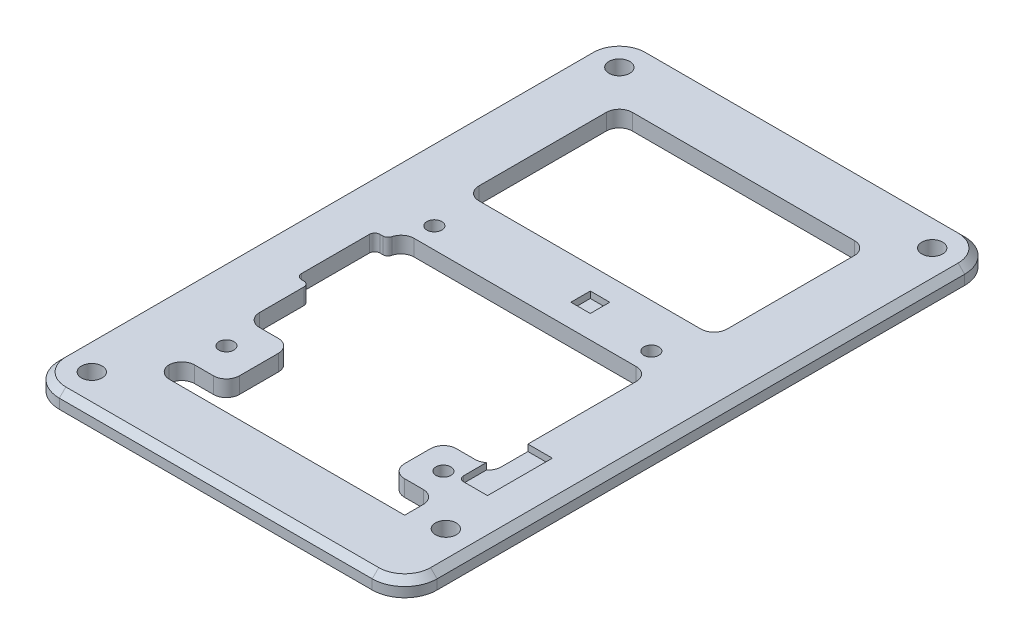
SolidWorks part; units mm, degrees
ref_plane "Front Plane" through (0, 0, 0) normal (0, 0, 1) x (1, 0, 0)
ref_plane "Top Plane" through (0, 0, 0) normal (0, 1, 0) x (1, 0, 0)
ref_plane "Right Plane" through (0, 0, 0) normal (1, 0, 0) x (0, 0, -1)
sketch "Sketch1" plane through (0, 0, 0) normal (0, 1, 0) x (1, 0, 0)
  line L4 (26.75, 55.875) -> (-26.75, 55.875)
  line L5 (26.75, -45.825) -> (26.75, 55.875)
  line L6 (-26.75, -45.825) -> (26.75, -45.825)
  line L7 (-26.75, 55.875) -> (-26.75, -45.825)
  line L8 (26.75, 55.875) -> (-26.75, 55.875)
  line L9 (26.75, -45.825) -> (26.75, 55.875)
  line L10 (-26.75, -45.825) -> (26.75, -45.825)
  line L11 (-26.75, 55.875) -> (-26.75, -45.825)
  line L12 (3.325, 28.475) -> (-2.675, 28.475)
  line L13 (3.325, 24.185) -> (3.325, 28.475)
  line L14 (-2.675, 24.185) -> (3.325, 24.185)
  line L15 (-2.675, 28.475) -> (-2.675, 24.185)
  line L16 (3.325, 28.475) -> (-2.675, 28.475)
  line L17 (3.325, 24.185) -> (3.325, 28.475)
  line L18 (-2.675, 24.185) -> (3.325, 24.185)
  line L19 (-2.675, 28.475) -> (-2.675, 24.185)
  line L20 (-2.675, 4.275) -> (3.325, 4.275)
  line L21 (3.325, 4.275) -> (3.325, 8.565)
  line L22 (3.325, 8.565) -> (-2.675, 8.565)
  line L23 (-2.675, 8.565) -> (-2.675, 4.275)
  line L24 (-2.675, 4.275) -> (3.325, 4.275)
  line L25 (3.325, 4.275) -> (3.325, 8.565)
  line L26 (3.325, 8.565) -> (-2.675, 8.565)
  line L27 (-2.675, 8.565) -> (-2.675, 4.275)
  circle A1 centre (24.125, -34.325) radius 1.5
  circle A2 centre (24.125, -34.325) radius 1.5
  circle A3 centre (-24.125, -40.675) radius 1.5
  circle A4 centre (-24.125, -40.675) radius 1.5
  circle A5 centre (24.125, 40.675) radius 1.5
  circle A6 centre (24.125, 40.675) radius 1.5
  circle A7 centre (-24.125, 40.675) radius 1.5
  circle A8 centre (-24.125, 40.675) radius 1.5
  dimension "D1" = 0
  dimension "D2" = 0
  dimension "D3" = 0
  dimension "D4" = 0
  dimension "D5" = 0
  dimension "D6" = 0
  dimension "D7" = 0
sketch "Sketch2" plane through (0, 0, 0) normal (0, 1, 0) x (1, 0, 0)
  line L0 (-24.125, 40.675) -> (24.125, 40.675) construction
  line L1 (24.125, 40.675) -> (24.125, -40.675) construction
  line L2 (24.125, -40.675) -> (-24.125, -40.675) construction
  line L3 (-24.125, -40.675) -> (-24.125, 40.675) construction
  line L4 (-29.125, -45.675) -> (-29.125, 45.675)
  line L5 (-29.125, 45.675) -> (29.125, 45.675)
  line L6 (29.125, 45.675) -> (29.125, -45.675)
  line L7 (29.125, -45.675) -> (-29.125, -45.675)
  line L8 (-19.125, -35.675) -> (-19.125, 35.675)
  line L9 (-19.125, 35.675) -> (19.125, 35.675)
  line L10 (19.125, 35.675) -> (19.125, -35.675)
  line L11 (19.125, -35.675) -> (-19.125, -35.675)
  circle A0 centre (24.125, 40.675) radius 1.5 construction
  circle A1 centre (24.125, -34.325) radius 1.5 construction
  circle A2 centre (-24.125, -40.675) radius 1.5 construction
  circle A3 centre (-24.125, 40.675) radius 1.5 construction
  circle A4 centre (24.125, 40.675) radius 1.5
  circle A5 centre (24.125, -34.325) radius 1.5
  circle A6 centre (-24.125, -40.675) radius 1.5
  circle A7 centre (-24.125, 40.675) radius 1.5
  dimension "D1" = 5
  dimension "D2" = 5
sketch "Sketch3" plane through (0, 0, 0) normal (0, 1, 0) x (1, 0, 0)
  line L0 (29.125, -45.675) -> (-29.125, -45.675) construction
  line L1 (-23.5, 9.325) -> (23.5, 9.325)
  line L2 (-23.5, 9.325) -> (-23.5, -30.675)
  line L3 (-23.5, -30.675) -> (23.5, -30.675)
  line L4 (23.5, 9.325) -> (23.5, -30.675)
  line L5 (-23.5, 9.325) -> (23.5, -30.675)
  line L6 (-23.5, -30.675) -> (23.5, 9.325)
  line L7 (-20.5, -0.675) -> (-14.9, -0.675)
  line L8 (-20.5, -0.675) -> (-20.5, -11.575)
  line L9 (-20.5, -11.575) -> (-14.9, -11.575)
  line L10 (-14.9, -0.675) -> (-14.9, -11.575)
  line L11 (5.2, -6.775) -> (16.8, -6.775)
  line L12 (5.2, -6.775) -> (5.2, -21.775)
  line L13 (5.2, -21.775) -> (16.8, -21.775)
  line L14 (16.8, -6.775) -> (16.8, -21.775)
  line L16 (18.4, -16.675) -> (22.9, -16.675)
  line L18 (18.4, -16.675) -> (18.4, -26.675)
  line L19 (18.4, -26.675) -> (22.9, -26.675)
  line L20 (22.9, -16.675) -> (22.9, -26.675)
  line L21 (3.5, 8.575) -> (6.5, 8.575)
  line L22 (3.5, 8.575) -> (3.5, 5.575)
  line L23 (3.5, 5.575) -> (6.5, 5.575)
  line L24 (6.5, 8.575) -> (6.5, 5.575)
  circle A0 centre (-17.23, -26.805) radius 1.27
  circle A1 centre (16.23, -26.805) radius 1.27
  circle A2 centre (-17.23, 5.255) radius 1.27
  circle A3 centre (16.23, 5.255) radius 1.27
  point P0 (0, -10.675)
  point P21 (16.23, 6.525)
  point P23 (-18.5, 5.255)
  point P24 (17.5, 5.255)
  point P27 (16.23, -28.075)
  dimension "D15" = 2.54
  dimension "D1" = 47
  dimension "D2" = 40
  dimension "D3" = 10.9
  dimension "D4" = 5.6
  dimension "D5" = 3
  dimension "D6" = 10
  dimension "D7" = 11.6
  dimension "D8" = 15
  dimension "D9" = 8.9
  dimension "D10" = 6.7
  dimension "D11" = 5
  dimension "D12" = 6
  dimension "D13" = 2.8
  dimension "D14" = 2.6
  dimension "D16" = 15
  dimension "D17" = 10
  dimension "D18" = 4
  dimension "D19" = 0.6
  dimension "D20" = 4.5
  dimension "D21" = 3
  dimension "D22" = 0.75
  dimension "D23" = 17
sketch "Sketch5" plane through (0, 0, 0) normal (0, 1, 0) x (1, 0, 0)
  line L0 (-19.125, 2.025) -> (19.125, 2.025)
  line L1 (-23.5, 9.325) -> (23.5, 9.325) construction
  line L2 (-19.125, 12.025) -> (19.125, 12.025)
  line L3 (-19.125, 2.025) -> (-19.125, -21.805)
  line L4 (-19.125, 35.675) -> (-19.125, -35.675)
  line L5 (19.125, 35.675) -> (-19.125, 35.675)
  line L6 (19.125, -35.675) -> (19.125, 35.675)
  line L7 (-19.125, -35.675) -> (19.125, -35.675)
  line L8 (-19.125, 35.675) -> (-19.125, 12.025)
  line L9 (19.125, 35.675) -> (-19.125, 35.675)
  line L10 (19.125, -35.675) -> (19.125, -30.805)
  line L11 (-19.125, -35.675) -> (19.125, -35.675)
  line L12 (29.125, -45.675) -> (29.125, 45.675)
  line L13 (29.125, 45.675) -> (-29.125, 45.675)
  line L14 (-29.125, 45.675) -> (-29.125, -45.675)
  line L15 (-29.125, -45.675) -> (29.125, -45.675)
  line L16 (29.125, -45.675) -> (29.125, 45.675)
  line L17 (29.125, 45.675) -> (-29.125, 45.675)
  line L18 (-29.125, 45.675) -> (-29.125, -45.675)
  line L19 (-29.125, -45.675) -> (29.125, -45.675)
  line L20 (19.125, 12.025) -> (19.125, 35.675)
  line L21 (-19.125, -31.805) -> (-19.125, -35.675)
  line L22 (-19.125, -21.805) -> (-12.23, -21.805)
  line L28 (-19.125, -31.805) -> (-12.23, -31.805)
  line L29 (-12.23, -21.805) -> (-12.23, -31.805)
  line L30 (19.125, -22.805) -> (12.23, -22.805)
  line L32 (19.125, -30.805) -> (12.23, -30.805)
  line L33 (12.23, -22.805) -> (12.23, -30.805)
  line L34 (19.125, -22.805) -> (19.125, 2.025)
  line L35 (16.23, -26.805) -> (16.23, -30.805) construction
  line L36 (16.23, -26.805) -> (12.23, -26.805) construction
  line L37 (-17.23, -26.805) -> (-12.23, -26.805) construction
  line L39 (-17.23, -26.805) -> (-17.23, -31.805) construction
  circle A0 centre (-17.23, 5.255) radius 1.15
  circle A2 centre (-24.125, 40.675) radius 1.6
  circle A4 centre (-24.125, -40.675) radius 1.6
  circle A6 centre (24.125, -34.325) radius 1.6
  circle A8 centre (24.125, 40.675) radius 1.6
  circle A9 centre (-17.23, -26.805) radius 1.27
  circle A10 centre (-17.23, -26.805) radius 1.27 construction
  circle A11 centre (16.23, 5.255) radius 1.27
  circle A12 centre (16.23, 5.255) radius 1.27 construction
  circle A13 centre (-17.23, 5.255) radius 1.27
  circle A14 centre (-17.23, 5.255) radius 1.27 construction
  circle A15 centre (16.23, -26.805) radius 1.27
  circle A16 centre (16.23, -26.805) radius 1.27 construction
  circle A17 centre (16.23, 5.255) radius 1.15
  circle A18 centre (16.23, -26.805) radius 1.15
  circle A19 centre (-17.23, -26.805) radius 1.15
  point P3 (12.23, -23.8522)
  point P46 (12.23, -26.805)
  point P47 (-12.23, -26.805)
  dimension "D14" = 2.3
  dimension "D2" = 3.2
  dimension "D11" = 7.3
  dimension "D12" = 10
  dimension "D3" = 10
  dimension "D4" = 8
  dimension "D5" = 0
  dimension "D6" = 0
  dimension "D7" = 0
  dimension "D8" = 0
  dimension "D9" = 0
  dimension "D10" = 0
extrude "Boss-Extrude1" add sketch "Sketch5" along normal blind 2.5
sketch "Sketch8" plane through (0, 2.5, 0) normal (0, 1, 0) x (1, 0, 0)
  line L0 (18.4, -16.675) -> (22.9, -16.675) construction
  line L1 (18.4, -16.675) -> (18.4, -26.675) construction
  line L2 (22.9, -16.675) -> (22.9, -26.675) construction
  line L3 (18.4, -26.675) -> (22.9, -26.675) construction
  line L4 (18.4, -16.675) -> (22.9, -16.675)
  line L5 (18.4, -16.675) -> (18.4, -26.675)
  line L6 (22.9, -16.675) -> (22.9, -26.675)
  line L7 (18.4, -26.675) -> (22.9, -26.675)
  line L8 (3.5, 8.575) -> (3.5, 5.575) construction
  line L9 (3.5, 8.575) -> (6.5, 8.575) construction
  line L10 (6.5, 8.575) -> (6.5, 5.575) construction
  line L11 (3.5, 5.575) -> (6.5, 5.575) construction
  line L12 (3.5, 8.575) -> (3.5, 5.575)
  line L13 (3.5, 8.575) -> (6.5, 8.575)
  line L14 (6.5, 8.575) -> (6.5, 5.575)
  line L15 (3.5, 5.575) -> (6.5, 5.575)
extrude "Cut-Extrude1" cut sketch "Sketch8" against normal blind 1
fillet "Fillet1" radius 2 15 edges at (19.125, 1.25, -12.025) (19.125, 1.25, -35.675) (-19.125, 1.25, -12.025) (-19.125, 1.25, -35.675) (19.125, 1.25, -2.025) (-19.125, 1.25, -2.025) (-19.125, 1.25, 21.805) (19.125, 0.75, 22.805) (19.125, 1.25, 30.805) (-19.125, 1.25, 31.805) (-19.125, 1.25, 35.675) (12.23, 1.25, 30.805) (12.23, 1.25, 22.805) (-12.23, 1.25, 31.805) (-12.23, 1.25, 21.805)
fillet "Fillet2" radius 5 4 edges at (29.125, 1.25, 45.675) (-29.125, 1.25, 45.675) (-29.125, 1.25, -45.675) (29.125, 1.25, -45.675)
sketch "Sketch9" plane through (0, 0, 0) normal (0, -1, 0) x (1, 0, 0)
  line L0 (-14.9, 0.675) -> (-14.9, 11.575) construction
  line L1 (-20.5, 11.575) -> (-14.9, 11.575) construction
  line L2 (-20.5, 0.675) -> (-14.9, 0.675) construction
  line L3 (-20.5, 0.675) -> (-20.5, 11.575) construction
  line L4 (-14.9, 0.675) -> (-14.9, 11.575) construction
  line L5 (-20.5, 11.575) -> (-14.9, 11.575) construction
  line L6 (-20.5, 0.675) -> (-14.9, 0.675) construction
  line L7 (-20.5, 0.675) -> (-20.5, 11.575) construction
  line L8 (-14.3, 0.075) -> (-14.3, 12.175)
  line L9 (-21.1, 12.175) -> (-14.3, 12.175)
  line L10 (-21.1, 0.075) -> (-21.1, 12.175)
  line L11 (-21.1, 0.075) -> (-14.3, 0.075)
  dimension "D1" = 0.6
extrude "Cut-Extrude2" cut sketch "Sketch9" against normal through all
sketch "Sketch10" plane through (0, 0, 0) normal (0, 1, 0) x (1, 0, 0)
  line L0 (3.325, 4.275) -> (3.325, 8.565) construction
  line L1 (-2.675, 4.275) -> (3.325, 4.275) construction
  line L2 (3.325, 8.565) -> (-2.675, 8.565) construction
  line L3 (-2.675, 8.565) -> (-2.675, 4.275) construction
  line L4 (3.325, 4.275) -> (3.325, 8.565) construction
  line L5 (-2.675, 4.275) -> (3.325, 4.275) construction
  line L6 (3.325, 8.565) -> (-2.675, 8.565) construction
  line L7 (-2.675, 8.565) -> (-2.675, 4.275) construction
  line L8 (3.925, 3.675) -> (3.925, 9.165)
  line L9 (3.925, 9.165) -> (-3.275, 9.165)
  line L10 (-3.275, 9.165) -> (-3.275, 3.675)
  line L11 (-3.275, 3.675) -> (3.925, 3.675)
  dimension "D1" = 0.6
extrude "Cut-Extrude3" cut sketch "Sketch10" along normal blind 1
fillet "Fillet3" radius 0.8 9 edges at (-19.125, 1.25, 12.175) (-21.1, 1.25, 12.175) (-19.125, 1.25, 0.075) (-21.1, 1.25, 0.075) (3.925, 0.5, -3.675) (3.925, 0.5, -9.165) (-3.275, 0.5, -9.165) (-3.275, 0.5, -3.675) (18.4, 2, 26.675)
chamfer "Chamfer3" distance 1 angle 45 8 edges at (0, 2.5, 45.675) (27.6605, 2.5, 44.2105) (-27.6605, 2.5, 44.2105) (29.125, 2.5, 0) (-29.125, 2.5, 0) (27.6605, 2.5, -44.2105) (-27.6605, 2.5, -44.2105) (0, 2.5, -45.675)
